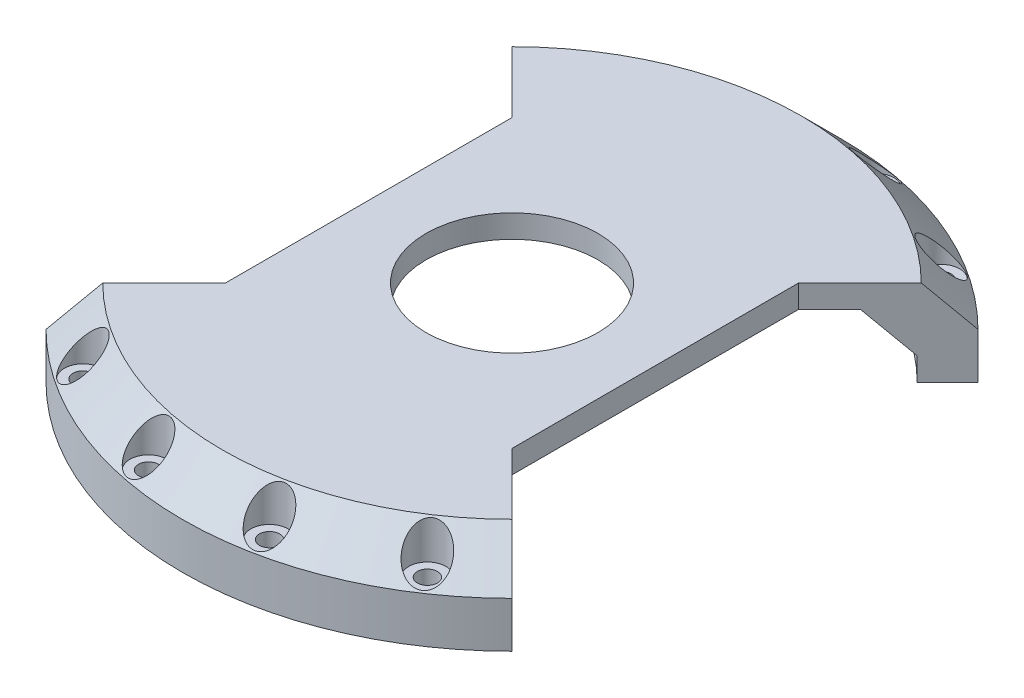
SolidWorks part; units mm, degrees
ref_plane "Front Plane" through (0, 0, 0) normal (0, 0, 1) x (1, 0, 0)
ref_plane "Top Plane" through (0, 0, 0) normal (0, 1, 0) x (1, 0, 0)
ref_plane "Right Plane" through (0, 0, 0) normal (1, 0, 0) x (0, 0, -1)
sketch "Sketch1" plane through (0, 0, 0) normal (0, 1, 0) x (1, 0, 0)
  circle A0 centre (0, 0) radius 57.5
  dimension "D1" = 115
extrude "Boss-Extrude1" add sketch "Sketch1" along normal blind 15
sketch "Sketch2" plane through (0, 0, 0) normal (0, -1, 0) x (1, 0, 0)
  circle A0 centre (0, 0) radius 50
  dimension "D1" = 100
extrude "Cut-Extrude1" cut sketch "Sketch2" against normal blind 11
sketch "Sketch3" plane through (0, 15, 0) normal (0, 1, 0) x (1, 0, 0)
  line L0 (0, 0) -> (0, 54) construction
  line L1 (0, 0) -> (-10.6273, 52.9439) construction
  circle A0 centre (0, 0) radius 54 construction
  circle A13 centre (0, 0) radius 15
  circle A14 centre (-10.6273, 52.9439) radius 1.75
  circle A15 centre (10.4424, 52.9807) radius 1.75
  circle A16 centre (29.9224, 44.9517) radius 1.75
  circle A17 centre (44.8469, 30.0791) radius 1.75
  circle A18 centre (52.9439, 10.6273) radius 1.75
  circle A19 centre (52.9807, -10.4424) radius 1.75
  circle A20 centre (44.9517, -29.9224) radius 1.75
  circle A21 centre (30.0791, -44.8469) radius 1.75
  circle A22 centre (10.6273, -52.9439) radius 1.75
  circle A23 centre (-10.4424, -52.9807) radius 1.75
  circle A24 centre (-29.9224, -44.9517) radius 1.75
  circle A25 centre (-44.8469, -30.0791) radius 1.75
  circle A26 centre (-52.9439, -10.6273) radius 1.75
  circle A27 centre (-52.9807, 10.4424) radius 1.75
  circle A28 centre (-44.9517, 29.9224) radius 1.75
  circle A29 centre (-30.0791, 44.8469) radius 1.75
  point P29 (0, 0)
  point P40 (0, 0)
  dimension "D1" = 108
  dimension "D2" = 11.35
  dimension "D4" = 30
  dimension "D3" = 3.5
extrude "Cut-Extrude2" cut sketch "Sketch3" against normal blind 15
sketch "Sketch4" plane through (0, 15, 0) normal (0, 1, 0) x (1, 0, 0)
  line L0 (25, 25) -> (40.6586, 40.6586)
  line L1 (-25, 25) -> (25, 25) construction
  line L2 (-25, 25) -> (-25, -25) construction
  line L3 (-25, -25) -> (25, -25) construction
  line L4 (25, 25) -> (25, -25)
  line L5 (-25, 25) -> (25, -25) construction
  line L6 (-25, -25) -> (25, 25) construction
  line L7 (25, -25) -> (40.6586, -40.6586)
  circle A0 centre (0, 0) radius 57.5 construction
  arc A1 (40.6586, -40.6586) -> (40.6586, 40.6586) centre (0, 0) ccw
  point P0 (0, 0)
  dimension "D1" = 50
extrude "Cut-Extrude3" cut sketch "Sketch4" against normal blind 15
mirror "Mirror1" about plane through (0, 0, 0) normal (1, 0, 0) of "Cut-Extrude3"
chamfer "Chamfer1" distance 7 angle 45 4 edges at (0, 15, -57.5) (0, 15, 57.5) (0, 11, 50) (0, 11, -50)
sketch "Sketch5" plane through (0, 15, 0) normal (0, 1, 0) x (1, 0, 0)
  line L0 (0, 0) -> (-10.6273, 52.9439) construction
  circle A0 centre (0, 0) radius 54 construction
  circle A1 centre (-10.6273, 52.9439) radius 3.25
  circle A2 centre (10.4424, 52.9807) radius 3.25
  circle A3 centre (29.9224, 44.9517) radius 3.25
  circle A4 centre (44.8469, 30.0791) radius 3.25
  circle A5 centre (52.9439, 10.6273) radius 3.25
  circle A6 centre (52.9807, -10.4424) radius 3.25
  circle A7 centre (44.9517, -29.9224) radius 3.25
  circle A8 centre (30.0791, -44.8469) radius 3.25
  circle A9 centre (10.6273, -52.9439) radius 3.25
  circle A10 centre (-10.4424, -52.9807) radius 3.25
  circle A11 centre (-29.9224, -44.9517) radius 3.25
  circle A12 centre (-44.8469, -30.0791) radius 3.25
  circle A13 centre (-52.9439, -10.6273) radius 3.25
  circle A14 centre (-52.9807, 10.4424) radius 3.25
  circle A15 centre (-44.9517, 29.9224) radius 3.25
  circle A16 centre (-30.0791, 44.8469) radius 3.25
  point P32 (0, 0)
  point P41 (0, 0)
  dimension "D1" = 6.5
extrude "Cut-Extrude4" cut sketch "Sketch5" against normal blind 7
